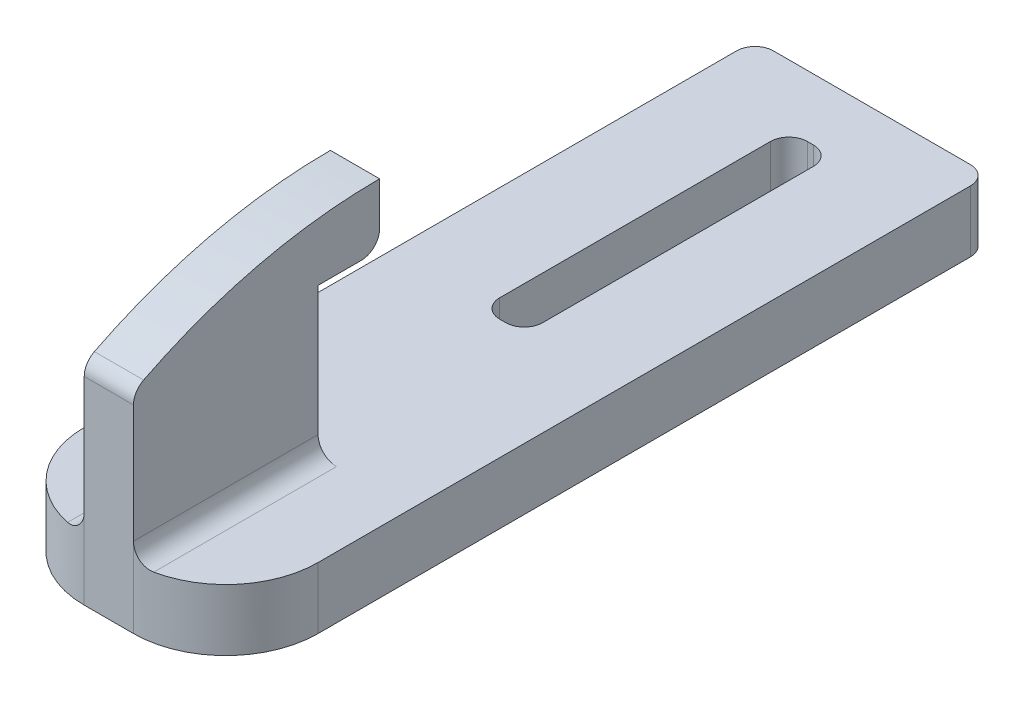
SolidWorks part; units mm, degrees
ref_plane "Front Plane" through (0, 0, 0) normal (0, 0, 1) x (1, 0, 0)
ref_plane "Top Plane" through (0, 0, 0) normal (0, 1, 0) x (1, 0, 0)
ref_plane "Right Plane" through (0, 0, 0) normal (1, 0, 0) x (0, 0, -1)
sketch "Sketch1" plane through (0, 0, 0) normal (0, 1, 0) x (1, 0, 0)
  line L1 (0, 0) -> (-19, 0)
  line L2 (0, 0) -> (0, 62)
  line L3 (0, 62) -> (-19, 62)
  line L4 (-19, 0) -> (-19, 62)
  line L5 (-11.25, 57) -> (-7.75, 57)
  line L6 (-11.25, 57) -> (-11.25, 32)
  line L7 (-11.25, 32) -> (-7.75, 32)
  line L8 (-7.75, 57) -> (-7.75, 32)
  point P9 (-9.5, 57)
  point P10 (-9.5, 62)
  dimension "D1" = 62
  dimension "D2" = 19
  dimension "D3" = 3.5
  dimension "D4" = 5
  dimension "D5" = 25
extrude "Boss-Extrude1" add sketch "Sketch1" along normal blind 5
sketch "Sketch4" plane through (0, 5, 0) normal (0, 1, 0) x (1, 0, 0)
  line L0 (0, 62) -> (-19, 62) construction
  line L1 (-11.5, 15) -> (-7.5, 15)
  line L2 (-11.5, 15) -> (-11.5, 0)
  line L3 (-11.5, 0) -> (-7.5, 0)
  line L4 (-7.5, 15) -> (-7.5, 0)
  line L5 (0, 62) -> (-19, 62) construction
  point P6 (-9.5, 62)
  point P7 (-9.5, 15)
  dimension "D1" = 4
  dimension "D2" = 15
  dimension "D3" = 47
extrude "Boss-Extrude3" add sketch "Sketch4" along normal blind 12
sketch "Sketch5" plane through (-7.5, 0, 0) normal (1, 0, 0) x (0, 0, -1)
  line L0 (15, 17) -> (20, 17)
  line L1 (20, 17) -> (20, 22)
  line L2 (20, 22) -> (78.519, 22) construction
  line L3 (0, 17) -> (15, 17)
  arc A0 (0, 17) -> (20, 22) centre (20, -20.5) cw
  dimension "D1" = 5
  dimension "D2" = 5
extrude "Boss-Extrude4" add sketch "Sketch5" against normal blind 4
sketch "Sketch6" plane through (0, 5, 0) normal (0, 1, 0) x (1, 0, 0)
  line L0 (-19, 62) -> (-19, 0) construction
  line L1 (-19, 7.5) -> (-19, 0)
  line L2 (-19, 0) -> (-11.5, 0)
  line L3 (-9.5, 0) -> (-9.5, 20) construction
  line L4 (-11.5, 0) -> (-7.5, 0) construction
  line L5 (-11.5, 20) -> (-7.5, 20) construction
  line L6 (0, 0) -> (-7.5, 0)
  line L7 (0, 7.5) -> (0, 0)
  arc A0 (-11.5, 0) -> (-19, 7.5) centre (-11.5, 7.5) cw
  arc A1 (-7.5, 0) -> (0, 7.5) centre (-7.5, 7.5) ccw
extrude "Cut-Extrude1" cut sketch "Sketch6" against normal through all
fillet "Fillet1" radius 1.5 10 edges at (-9.5, 17, -20) (-9.5, 17, 0) (-11.25, 2.5, -57) (-7.75, 2.5, -57) (-7.75, 2.5, -32) (-11.25, 2.5, -32) (-19, 2.5, -62) (0, 2.5, -62) (-11.5, 5, -7.5) (-7.5, 5, -7.5)
